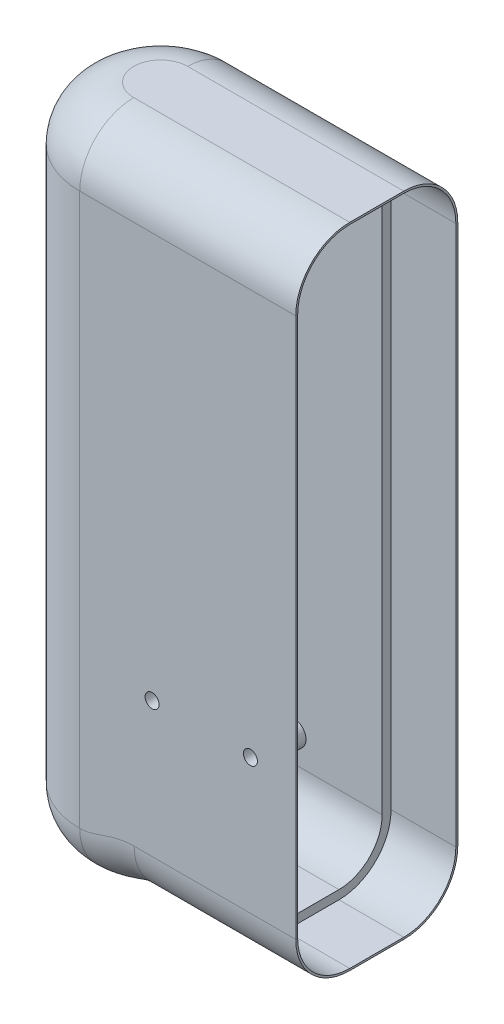
SolidWorks part; units mm, degrees
ref_plane "Front Plane" through (0, 0, 0) normal (0, 0, 1) x (1, 0, 0)
ref_plane "Top Plane" through (0, 0, 0) normal (0, 1, 0) x (1, 0, 0)
ref_plane "Right Plane" through (0, 0, 0) normal (1, 0, 0) x (0, 0, -1)
sketch "Sketch1" plane through (0, 0, 0) normal (0, 1, 0) x (1, 0, 0)
  line L0 (0, 19.05) -> (50.8, 19.05)
  line L1 (50.8, 19.05) -> (50.8, -19.05)
  line L2 (50.8, -19.05) -> (0, -19.05)
  arc A0 (0, 19.05) -> (0, -19.05) centre (0, 0) ccw
  dimension "D1" = 38.1
  dimension "D2" = 50.8
extrude "Boss-Extrude1" add sketch "Sketch1" along normal mid plane 152.4
sketch "Sketch2" plane through (0, -76.2, 0) normal (0, -1, 0) x (1, 0, 0)
  circle A0 centre (0, 0) radius 14.2875
  dimension "D1" = 28.575
extrude "Cut-Extrude1" cut sketch "Sketch2" against normal blind 114.3
fillet "Fillet1" radius 12.7 5 edges at (25.4, 76.2, -19.05) (25.4, 76.2, 19.05) (25.4, -76.2, -19.05) (25.4, -76.2, 19.05) (-19.05, 76.2, 0)
sketch "Sketch3" plane through (50.8, 0, 0) normal (1, 0, 0) x (0, 0, -1)
  line L8 (16.51, -63.5) -> (16.51, 63.5)
  line L9 (6.35, 73.66) -> (-6.35, 73.66)
  line L10 (-16.51, 63.5) -> (-16.51, -63.5)
  line L11 (-6.35, -73.66) -> (6.35, -73.66)
  line L12 (16.51, -63.5) -> (16.51, 63.5)
  line L13 (6.35, 73.66) -> (-6.35, 73.66)
  line L14 (-16.51, 63.5) -> (-16.51, -63.5)
  line L15 (-6.35, -73.66) -> (6.35, -73.66)
  arc A8 (16.51, 63.5) -> (6.35, 73.66) centre (6.35, 63.5) ccw
  arc A9 (-6.35, 73.66) -> (-16.51, 63.5) centre (-6.35, 63.5) ccw
  arc A10 (-16.51, -63.5) -> (-6.35, -73.66) centre (-6.35, -63.5) ccw
  arc A11 (6.35, -73.66) -> (16.51, -63.5) centre (6.35, -63.5) ccw
  arc A12 (16.51, 63.5) -> (6.35, 73.66) centre (6.35, 63.5) ccw
  arc A13 (-6.35, 73.66) -> (-16.51, 63.5) centre (-6.35, 63.5) ccw
  arc A14 (-16.51, -63.5) -> (-6.35, -73.66) centre (-6.35, -63.5) ccw
  arc A15 (6.35, -73.66) -> (16.51, -63.5) centre (6.35, -63.5) ccw
  dimension "D1" = 2.54
extrude "Cut-Extrude2" cut sketch "Sketch3" against normal blind 44.45
sketch "Sketch4" plane through (0, 38.1, 0) normal (0, -1, 0) x (1, 0, 0)
  line L1 (3.81, 11.1125) -> (6.35, 11.1125)
  line L2 (3.81, -11.1125) -> (3.81, 11.1125)
  line L5 (6.35, -12.7988) -> (6.35, 12.7988) construction
  line L6 (3.81, -11.1125) -> (6.35, -11.1125)
  line L7 (6.35, -11.1125) -> (6.35, 11.1125)
  arc A2 (3.81, 11.1125) -> (3.81, -11.1125) centre (0, 0) ccw
  arc A3 (3.81, 11.1125) -> (3.81, -11.1125) centre (0, 0) ccw
  dimension "D1" = 2.54
extrude "Cut-Extrude3" cut sketch "Sketch4" against normal blind 31.75
sketch "Sketch6" plane through (50.8, 0, 0) normal (1, 0, 0) x (0, 0, -1)
  line L0 (-18.5992, 63.5) -> (-18.5992, -63.5)
  line L1 (-6.35, -75.7492) -> (6.35, -75.7492)
  line L2 (18.5992, -63.5) -> (18.5992, 63.5)
  line L3 (6.35, 75.7492) -> (-6.35, 75.7492)
  line L4 (19.05, -63.5) -> (19.05, 63.5)
  line L5 (6.35, 76.2) -> (-6.35, 76.2)
  line L6 (-19.05, 63.5) -> (-19.05, -63.5)
  line L7 (-6.35, -76.2) -> (6.35, -76.2)
  line L8 (19.05, -63.5) -> (19.05, 63.5) construction
  line L9 (6.35, 76.2) -> (-6.35, 76.2) construction
  line L10 (-19.05, 63.5) -> (-19.05, -63.5) construction
  line L11 (-6.35, -76.2) -> (6.35, -76.2) construction
  arc A0 (-6.35, 75.7492) -> (-18.5992, 63.5) centre (-6.35, 63.5) ccw
  arc A1 (-18.5992, -63.5) -> (-6.35, -75.7492) centre (-6.35, -63.5) ccw
  arc A2 (6.35, -75.7492) -> (18.5992, -63.5) centre (6.35, -63.5) ccw
  arc A3 (18.5992, 63.5) -> (6.35, 75.7492) centre (6.35, 63.5) ccw
  arc A4 (19.05, 63.5) -> (6.35, 76.2) centre (6.35, 63.5) ccw
  arc A5 (-6.35, 76.2) -> (-19.05, 63.5) centre (-6.35, 63.5) ccw
  arc A6 (-19.05, -63.5) -> (-6.35, -76.2) centre (-6.35, -63.5) ccw
  arc A7 (6.35, -76.2) -> (19.05, -63.5) centre (6.35, -63.5) ccw
  arc A8 (19.05, 63.5) -> (6.35, 76.2) centre (6.35, 63.5) ccw construction
  arc A9 (-6.35, 76.2) -> (-19.05, 63.5) centre (-6.35, 63.5) ccw construction
  arc A10 (-19.05, -63.5) -> (-6.35, -76.2) centre (-6.35, -63.5) ccw construction
  arc A11 (6.35, -76.2) -> (19.05, -63.5) centre (6.35, -63.5) ccw construction
  dimension "D1" = 0
  dimension "D2" = 0.4508
extrude "Cut-Extrude4" cut sketch "Sketch6" against normal blind 15.24
sketch "Sketch7" plane through (0, -76.2, 0) normal (0, -1, 0) x (1, 0, 0)
  circle A0 centre (18.415, 0) radius 2.25 construction
  circle A1 centre (18.415, 0) radius 2.25
extrude "Cut-Extrude5" cut sketch "Sketch7" against normal up to next
sketch "Sketch8" plane through (0, 0, 16.51) normal (0, 0, -1) x (-1, 0, 0)
  line L0 (-6.35, 63.5) -> (-6.35, -63.5) construction
  line L2 (-6.35, 63.5) -> (-6.35, -63.5) construction
  line L3 (-50.8, 63.5) -> (-50.8, -63.5) construction
  line L4 (-6.35, -31.75) -> (-50.8, -31.75) construction
  line L5 (-50.8, -76.2) -> (-12.7988, -76.2) construction
  line L6 (-28.575, -31.75) -> (-28.575, 49968.25) construction
  line L7 (-50.8, 63.5) -> (-50.8, -63.5) construction
  circle A0 centre (-17.018, -31.75) radius 1.651
  circle A1 centre (-40.132, -31.75) radius 1.651
  point P14 (-28.575, -31.75)
  dimension "D3" = 3.302
  dimension "D1" = 44.45
  dimension "D2" = 23.114
extrude "Cut-Extrude6" cut sketch "Sketch8" against normal through all
sketch "Sketch9" plane through (0, 0, 19.05) normal (0, 0, 1) x (1, 0, 0)
  circle A0 centre (40.132, -31.75) radius 1.651 construction
  circle A1 centre (17.018, -31.75) radius 1.651 construction
  circle A2 centre (40.132, -31.75) radius 1.651
  circle A3 centre (17.018, -31.75) radius 1.651
extrude "Extrude-Thin1" add sketch "Sketch9" against normal blind 10.16 thin thin type one direction wall 1.27
sketch "Sketch10" plane through (0, 0, 8.89) normal (0, 0, -1) x (-1, 0, 0)
  line L1 (-40.132, -28.829) -> (-17.018, -28.829)
  line L2 (-40.132, -28.829) -> (-40.132, -34.671)
  line L3 (-40.132, -34.671) -> (-17.018, -34.671)
  line L4 (-17.018, -28.829) -> (-17.018, -34.671)
  circle A0 centre (-40.132, -31.75) radius 2.921 construction
  circle A1 centre (-17.018, -31.75) radius 2.921 construction
extrude "Cut-Extrude7" cut sketch "Sketch10" against normal blind 2.54
